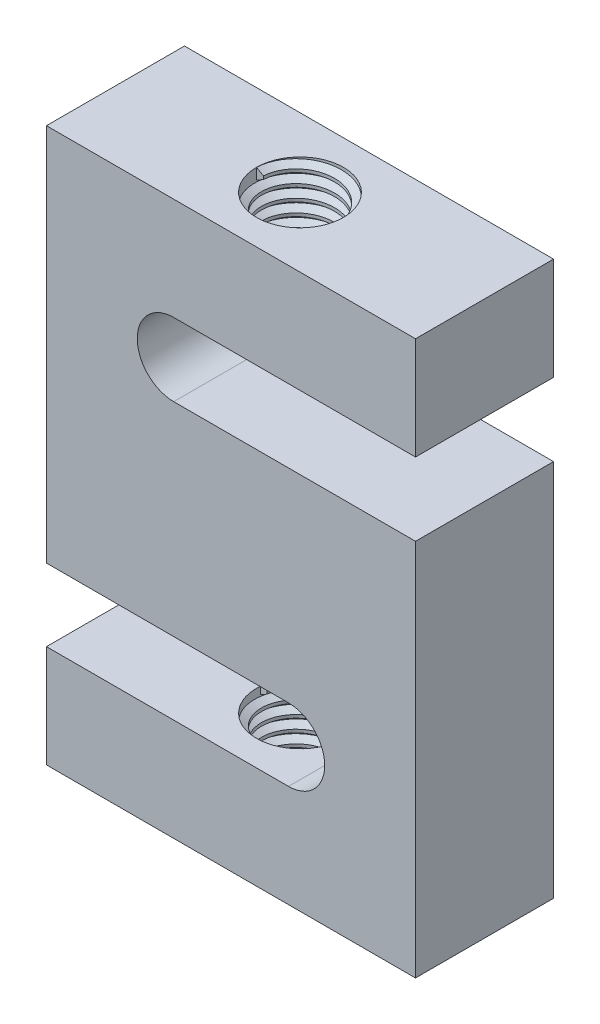
SolidWorks part; units mm, degrees
ref_plane "Front Plane" through (0, 0, 0) normal (0, 0, 1) x (1, 0, 0)
ref_plane "Top Plane" through (0, 0, 0) normal (0, 1, 0) x (1, 0, 0)
ref_plane "Right Plane" through (0, 0, 0) normal (1, 0, 0) x (0, 0, -1)
sketch "Sketch1" plane through (0, 0, 0) normal (0, 0, 1) x (1, 0, 0)
  line L0 (-12.9, 24) -> (25.4, 24) construction
  line L1 (25.4, -38.1) -> (-25.4, -38.1) construction
  line L2 (25.4, -38.1) -> (25.4, 38.1) construction
  line L3 (25.4, 38.1) -> (-25.4, 38.1) construction
  line L4 (-25.4, -38.1) -> (-25.4, 38.1) construction
  line L5 (25.4, -38.1) -> (-25.4, 38.1) construction
  line L6 (25.4, 38.1) -> (-25.4, -38.1) construction
  line L7 (12.9, 24) -> (12.9, 13.96) construction
  line L8 (-12.9, 24) -> (-12.9, 13.96) construction
  line L9 (-25.4, -24) -> (12.9, -24) construction
  line L10 (0, -38.1) -> (0, 38.1) construction
  line L11 (-12.9, 13.96) -> (25.4, 13.96) construction
  line L13 (-25.4, -14.04) -> (25.4, -14.04) construction
  line L14 (25.4, 13.96) -> (25.4, -14.04)
  line L15 (25.4, 18.98) -> (-25.4, 18.98) construction
  line L16 (25.4, -19.02) -> (-25.4, -19.02) construction
  line L17 (-7.88, 13.96) -> (-7.88, 24) construction
  line L18 (7.92, -24) -> (7.92, -14.04) construction
  line L19 (-12.9, -14.04) -> (-12.9, -24) construction
  line L20 (12.9, -14.04) -> (12.9, -24) construction
  line L21 (25.4, 24) -> (25.4, 38.1)
  line L22 (25.4, 38.1) -> (-25.4, 38.1)
  line L23 (-25.4, 38.1) -> (-25.4, -14.04)
  line L24 (25.4, -14.04) -> (25.4, -38.1)
  line L25 (25.4, -38.1) -> (-25.4, -38.1)
  line L26 (-25.4, -24) -> (-25.4, -38.1)
  line L27 (7.92, -14.04) -> (-25.4, -14.04)
  line L28 (7.92, -24) -> (-25.4, -24)
  line L29 (25.4, 13.96) -> (-7.88, 13.96)
  line L30 (25.4, 24) -> (-7.88, 24)
  arc A0 (-7.88, 24) -> (-7.88, 13.96) centre (-7.88, 18.98) ccw
  arc A1 (7.92, -24) -> (7.92, -14.04) centre (7.92, -19.02) ccw
  point P0 (0, 0)
  point P21 (0, 0)
  point P24 (0, 18.98)
  point P27 (0, -19.02)
  point P32 (-7.88, 18.98)
  point P36 (7.92, -19.02)
  point P37 (0, 0)
  point P38 (0, 0)
  point P39 (0, 0)
  point P40 (12.9, -24)
  point P41 (0, 0)
  point P42 (0, 0)
  point P43 (-25.4, 10.9071)
  point P44 (-25.4, 2.286)
  point P45 (-25.4, -13.4477)
  dimension "D1" = 76.2
  dimension "D2" = 50.8
  dimension "D3" = 14.1
  dimension "D4" = 12.5
  dimension "D5" = 12.5
  dimension "D6" = 14.1
  dimension "D7" = 28
  dimension "D8" = 10.04
extrude "Boss-Extrude1" add sketch "Sketch1" along normal blind 19
sketch "Sketch6" plane through (0, 38.1, 0) normal (0, 1, 0) x (1, 0, 0)
  line L0 (-25.4, 0) -> (25.4, -19) construction
  line L1 (-25.4, 0) -> (25.4, 0)
  line L2 (-25.4, 0) -> (-25.4, -19)
  line L3 (-25.4, -19) -> (25.4, -19)
  line L4 (25.4, 0) -> (25.4, -19)
  line L5 (25.4, 0) -> (-25.4, -19) construction
  circle A0 centre (0, -9.5) radius 5.98
  point P6 (0, -9.5)
  dimension "D1" = 11.96
extrude "Cut-Extrude1" cut sketch "Sketch6" against normal up to surface (14.1 mm away) contours A0 up to face at (8.76, 24, 9.5)
thread "Thread1" pitch 1.75 start angle 0, offset 0, length 0, pitch 1.75, diameter 11.96
ref_plane "Plane1" through (-5.98, 38.1, 9.5) normal (0, 0, 1) x (-1, 0, 0)
sketch "Thread Profile1" plane through (-5.98, 38.1, 9.5) normal (0, 0, 1) x (-1, 0, 0)
  line L0 (0, 0) -> (0, 1.75) construction
  line L11 (0, 0) -> (0, 1.5312)
  line L12 (0, 1.5312) -> (-0.9472, 0.9844)
  line L13 (-0.9472, 0.9844) -> (-0.9472, 0.5469)
  line L15 (-0.9472, 0.5469) -> (0, 0)
  line L17 (-0.9472, 0.7656) -> (0, 0.7656) construction
  point P2 (0, 0)
  dimension "Pitch" = 1.75
  dimension "Profile_Angle" = 60
  dimension "Profile_Land" = 0.4375
  dimension "Profile_Height" = 0.9472
sketch "Sketch11" plane through (0, -38.1, 0) normal (0, -1, 0) x (1, 0, 0)
  line L0 (-25.4, 19) -> (25.4, 0) construction
  line L1 (-25.4, 19) -> (25.4, 19)
  line L2 (-25.4, 19) -> (-25.4, 0)
  line L3 (-25.4, 0) -> (25.4, 0)
  line L4 (25.4, 19) -> (25.4, 0)
  line L5 (25.4, 19) -> (-25.4, 0) construction
  circle A0 centre (0, 9.5) radius 5.98
  dimension "D1" = 11.96
extrude "Cut-Extrude2" cut sketch "Sketch11" against normal up to surface (14.1 mm away) contours A0 up to face at (-8.74, -24, 9.5)
thread "Thread2" pitch 1.75 profile "Thread Profile2" start angle 0, offset 0, length 0, pitch 1.75, diameter 11.96
ref_plane "Plane2" through (5.98, -38.1, 9.5) normal (0, 0, 1) x (1, 0, 0)
sketch "Thread Profile2" plane through (5.98, -38.1, 9.5) normal (0, 0, 1) x (1, 0, 0)
  line L0 (0, 0) -> (0, 1.75) construction
  line L11 (0, 0) -> (0, 1.5312)
  line L12 (0, 1.5312) -> (-0.9472, 0.9844)
  line L13 (-0.9472, 0.9844) -> (-0.9472, 0.5469)
  line L15 (-0.9472, 0.5469) -> (0, 0)
  line L17 (-0.9472, 0.7656) -> (0, 0.7656) construction
  point P2 (0, 0)
  dimension "Pitch" = 1.75
  dimension "Profile_Angle" = 60
  dimension "Profile_Land" = 0.4375
  dimension "Profile_Height" = 0.9472
